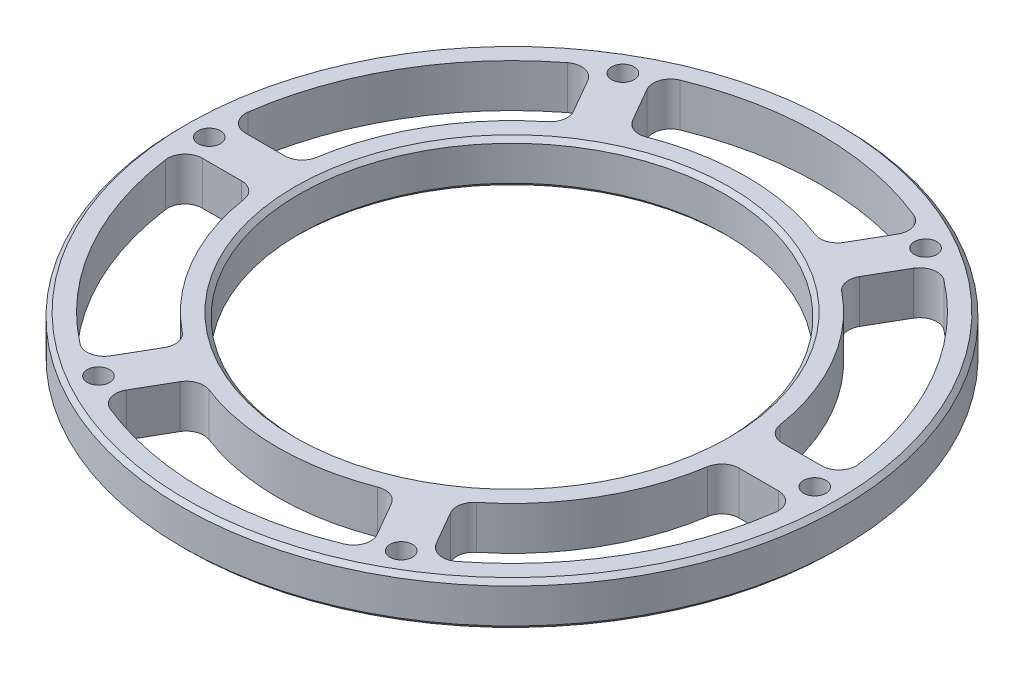
SolidWorks part; units mm, degrees
ref_plane "Front Plane" through (0, 0, 0) normal (0, 0, 1) x (1, 0, 0)
ref_plane "Top Plane" through (0, 0, 0) normal (0, 1, 0) x (1, 0, 0)
ref_plane "Right Plane" through (0, 0, 0) normal (1, 0, 0) x (0, 0, -1)
sketch "Sketch2" plane through (0, 0, 0) normal (1, 0, 0) x (0, 0, -1)
  line L0 (-49.2125, 0) -> (-76.2, 0)
  line L1 (-76.2, 0) -> (-76.2, 10)
  line L2 (-76.2, 10) -> (-49.2125, 10)
  line L3 (-49.2125, 10) -> (-49.2125, 0)
  dimension "D1" = 76.2
  dimension "D2" = 10
  dimension "D4" = 49.2125
ref_axis "Axis1" through (0, -0.5, 0) along (0, 1, 0)
revolve "Revolve1" add sketch "Sketch2" angle 360 about axis through (0, -0.5, 0) along (0, 1, 0)
hole_wizard "#6 (0.204) Diameter Hole1" positions "Sketch6" profile "Sketch7" hole size "#6" standard "ANSI Inch" end condition through all
sketch "Sketch6" plane through (0, 10, 0) normal (0, 1, 0) x (1, 0, 0)
  line L0 (0, 0) -> (-69.8201, 120.932) construction
  line L2 (0, 0) -> (0, 109.0908) construction
  point P0 (-35, 60.6218)
  dimension "D1" = 30
  dimension "D2" = 70
sketch "Sketch7" plane through (-35, 10, -60.6218) normal (1, 0, 0) x (0, 0, 1)
  line L0 (0, 0) -> (0, 10)
  line L1 (0, 10) -> (2.5908, 10)
  line L2 (2.5908, 10) -> (2.5908, 0)
  line L5 (2.5908, 0) -> (0, 0)
  line L11 (0, -6.35) -> (0, 107.95) construction
  dimension "Thru Hole Dia." = 5.1816
  dimension "Thru Hole Depth" = 10
pattern_circular "CirPattern3" count 6 over 360 about axis through (0, -0.5, 0) along (0, 1, 0) of "#6 (0.204) Diameter Hole1"
sketch "Sketch8" plane through (0, 10, 0) normal (0, 1, 0) x (1, 0, 0)
  line L4 (0, 0) -> (0, 93.9995) construction
  line L5 (-22.6606, 49.2493) -> (-31.182, 64.0088)
  line L6 (22.6606, 49.2493) -> (31.182, 64.0088)
  line L7 (0, 0) -> (-35, 60.6218) construction
  arc A0 (-22.6606, 49.2493) -> (22.6606, 49.2493) centre (0, 0) cw
  arc A1 (-31.182, 64.0088) -> (31.182, 64.0088) centre (0, 0) cw
  circle A2 centre (0, 0) radius 76.2 construction
  circle A4 centre (0, 0) radius 49.2125 construction
  dimension "D1" = 5
  dimension "D2" = 5
  dimension "D3" = 5
extrude "Cut-Extrude1" cut sketch "Sketch8" against normal through all
fillet "Fillet1" radius 4 4 edges at (-22.6606, 5, -49.2493) (22.6606, 5, -49.2493) (31.182, 5, -64.0088) (-31.182, 5, -64.0088)
pattern_circular "CirPattern4" count 6 over 360 about axis through (0, -0.5, 0) along (0, 1, 0) of "Cut-Extrude1", "Fillet1"
chamfer "Chamfer1" distance 1 angle 45 2 edges at (0, 10, -49.2125) (0, 0, -49.2125)
chamfer "Chamfer2" distance 1 angle 45 2 edges at (0, 10, -76.2) (0, 0, -76.2)
equation "\"TubeDiameter\" = 6.000in"
equation "\"D1@Sketch2\"=\"TubeDiameter\"/2"
